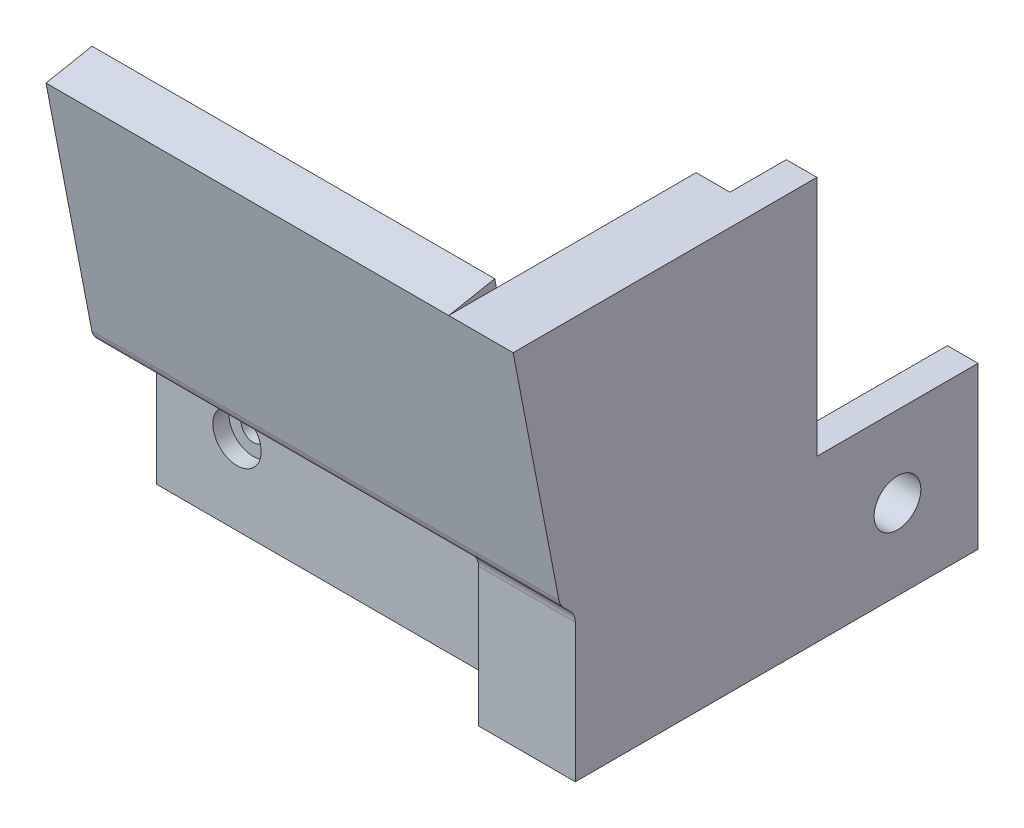
SolidWorks part; units mm, degrees
ref_plane "前视基准面" through (0, 0, 0) normal (0, 0, 1) x (1, 0, 0)
ref_plane "上视基准面" through (0, 0, 0) normal (0, 1, 0) x (1, 0, 0)
ref_plane "右视基准面" through (0, 0, 0) normal (1, 0, 0) x (0, 0, -1)
other "Configuration Table"
sketch "草图1" plane through (0, 0, 0) normal (1, 0, 0) x (0, 0, -1)
  line L0 (0, 0) -> (-10, 0)
  line L1 (-10, 0) -> (-17.7164, 40)
  line L2 (-17.7164, 40) -> (-12, 41.1027)
  line L3 (-12, 41.1027) -> (-6, 10)
  line L4 (-6, 10) -> (0, 10)
  line L5 (0, 10) -> (0, 0)
  dimension "D1" = 10
  dimension "D2" = 6
  dimension "D3" = 10
  dimension "D4" = 6
  dimension "D5" = 40
extrude "凸台-拉伸1" add sketch "草图1" along normal blind 50
sketch "草图2" plane through (0, 0, 0) normal (0, -1, 0) x (1, 0, 0)
  line L4 (0, 10) -> (0, 0)
  line L5 (0, 0) -> (50, 0)
  line L6 (50, 0) -> (50, 10)
  line L7 (50, 10) -> (0, 10)
  line L8 (0, 10) -> (0, 0)
  line L9 (0, 0) -> (50, 0)
  line L10 (50, 0) -> (50, 10)
  line L11 (50, 10) -> (0, 10)
  dimension "D1" = 0
extrude "凸台-拉伸2" add sketch "草图2" along normal blind 10
sketch "草图3" plane through (0, 0, 0) normal (-1, 0, 0) x (0, 0, 1)
  line L1 (0, 10) -> (10, 10)
  line L2 (0, 10) -> (0, -10)
  line L3 (0, -10) -> (10, -10)
  line L4 (10, 10) -> (10, -10)
extrude "凸台-拉伸3" add sketch "草图3" along normal blind 20
sketch "草图4" plane through (0, 10, 0) normal (0, 1, 0) x (1, 0, 0)
  line L1 (-20, 0) -> (0, 0)
  line L2 (-20, 0) -> (-20, -10)
  line L3 (-20, -10) -> (0, -10)
  line L4 (0, 0) -> (0, -10)
extrude "凸台-拉伸4" add sketch "草图4" along normal blind 30
sketch "草图5" plane through (50, 0, 0) normal (1, 0, 0) x (0, 0, -1)
  line L0 (-10, 10) -> (-11.9291, 10)
  line L1 (-17.7164, 40) -> (-10, 0) construction
  line L2 (-11.9291, 10) -> (-10, 0)
  line L3 (-10, 0) -> (-10, 10)
extrude "切除-拉伸1" cut sketch "草图5" against normal up to surface (50 mm away) up to face at (0, 27.9595, 12.4291)
chamfer "倒角1" distance 2 angle 45 1 edges at (25, 10, 10)
sketch "草图9" plane through (0, 0, 10) normal (0, 0, 1) x (1, 0, 0)
  line L0 (-20, 40) -> (-10, 40) construction
  line L1 (-20, 40) -> (0, 40) construction
  line L2 (-10, 40) -> (-10, 20) construction
  line L3 (50, -10) -> (50, 0) construction
  line L4 (50, -10) -> (50, 8) construction
  line L5 (50, 0) -> (10, 0) construction
  line L6 (-20, -10) -> (-20, 40) construction
  circle A0 centre (-10, 20) radius 1.5
  circle A1 centre (10, 0) radius 1.5
  dimension "D3" = 3
  dimension "D5" = 3
  dimension "D4" = 30
  dimension "D1" = 10
  dimension "D2" = 20
extrude "切除-拉伸2" cut sketch "草图9" against normal through all
sketch "草图12" plane through (0, 0, 10) normal (0, 0, 1) x (1, 0, 0)
  line L6 (0, 30.7352) -> (0, 40)
  line L7 (0, 30.7352) -> (0, 40)
  line L8 (0, 40) -> (-20, 40)
  line L9 (50, -10) -> (50, 8)
  line L10 (50, 8) -> (0, 8)
  line L11 (0, 8) -> (0, 30.7352)
  line L15 (50, -10) -> (50, 8)
  line L16 (50, 8) -> (0, 8)
  line L17 (0, 8) -> (0, 30.7352)
  line L19 (0, 40) -> (-20, 40)
  line L20 (-20, 40) -> (-20, -10)
  line L21 (-20, 40) -> (-20, -10)
  line L22 (-20, -10) -> (50, -10)
  line L23 (-20, -10) -> (50, -10)
  dimension "D1" = 0
extrude "切除-拉伸4" cut sketch "草图12" against normal blind 6
sketch "草图13" plane through (0, 8, 0) normal (0, -1, 0) x (1, 0, 0)
  line L0 (50, 4) -> (0, 4) construction
  line L1 (0, 10) -> (4, 10)
  line L2 (0, 10) -> (0, 4)
  line L3 (0, 4) -> (4, 4)
  line L4 (4, 10) -> (4, 4)
  line L6 (50, 10) -> (46, 10)
  line L7 (50, 10) -> (50, 4)
  line L8 (50, 4) -> (46, 4)
  line L9 (46, 10) -> (46, 4)
  dimension "D1" = 4
  dimension "D2" = 4
extrude "凸台-拉伸12" add sketch "草图13" along normal up to surface (18 mm away) up to face at (15, -10, 2)
fillet "圆角2" radius 2 3 edges at (25, 9.9121, 11.9121) (48, 8, 10) (2, 8, 10)
sketch "草图15" plane through (0, 0, 0) normal (0, 0, -1) x (-1, 0, 0)
  line L0 (-25, 10) -> (-25, 20.01) construction
  line L1 (0, 40) -> (20, 40) construction
  line L2 (0, 40) -> (0, -10) construction
  line L3 (0, -10) -> (20, -10) construction
  line L4 (20, 40) -> (20, -10) construction
  line L5 (-50, 10) -> (0, 10) construction
  line L6 (-50, -10) -> (-70, -10)
  line L7 (-70, 40) -> (-70, -10)
  line L8 (-50, 40) -> (-70, 40)
  line L9 (-50, 40) -> (-50, -10)
  circle A0 centre (10, 20) radius 1.5 construction
  circle A1 centre (-60, 20) radius 1.5
extrude "凸台-拉伸14" add sketch "草图15" against normal up to surface (4 mm away) up to face at (-8.5, 20, 4)
sketch "草图16" plane through (0, 0, 4) normal (0, 0, 1) x (1, 0, 0)
  line L5 (-20, -10) -> (0, -10)
  line L6 (0, -10) -> (0, 10)
  line L7 (0, 10) -> (0, 40)
  line L8 (0, 40) -> (-20, 40)
  line L9 (-20, 40) -> (-20, -10)
  line L10 (-20, -10) -> (0, -10)
  line L11 (0, -10) -> (0, 10)
  line L12 (0, 10) -> (0, 40)
  line L13 (0, 40) -> (-20, 40)
  line L14 (-20, 40) -> (-20, -10)
  dimension "D1" = 0
extrude "切除-拉伸5" cut sketch "草图16" against normal up to surface (4 mm away) up to face at (-8.5, 20, 0)
sketch "草图17" plane through (0, 0, 4) normal (0, 0, 1) x (1, 0, 0)
  line L0 (70, -10) -> (50, -10) construction
  line L1 (70, 40) -> (54, 40)
  line L2 (70, 40) -> (70, -10)
  line L3 (70, -10) -> (54, -10)
  line L4 (54, 40) -> (54, -10)
  dimension "D1" = 16
extrude "切除-拉伸6" cut sketch "草图17" against normal up to surface (4 mm away) up to face at (11.5, 0, 0)
sketch "草图18" plane through (50, 0, 0) normal (-1, 0, 0) x (0, 0, 1)
  line L0 (0, 10) -> (6, 10)
  line L1 (6, 10) -> (7.9291, 20)
  line L2 (6, 10) -> (12, 41.1027) construction
  line L3 (7.9291, 20) -> (0, 20)
  line L4 (0, 10) -> (0, 40) construction
  line L5 (0, 20) -> (0, 10)
  dimension "D1" = 10
extrude "凸台-拉伸15" add sketch "草图18" along normal blind 10
sketch "草图20" plane through (0, 0, 0) normal (0, 0, -1) x (-1, 0, 0)
  line L1 (-50, 40) -> (-54, 40)
  line L2 (-50, 40) -> (-50, -10)
  line L3 (-50, -10) -> (-54, -10)
  line L4 (-54, 40) -> (-54, -10)
extrude "凸台-拉伸16" add sketch "草图20" along normal blind 20
sketch "草图23" plane through (54, 0, 0) normal (1, 0, 0) x (0, 0, -1)
  line L0 (-4, -10) -> (-4, 20) construction
  line L1 (-4, 12) -> (20, 12)
  line L2 (-4, 12) -> (-4, -10)
  line L3 (-4, -10) -> (20, -10)
  line L4 (20, 12) -> (20, -10)
  line L5 (-7.9291, 20) -> (-4, 20) construction
  dimension "D1" = 8
extrude "切除-拉伸9" cut sketch "草图23" against normal up to surface (4 mm away) up to face at (50, 13.687, 9.9675)
sketch "草图24" plane through (0, 0, 4) normal (0, 0, 1) x (1, 0, 0)
  line L5 (50, 12) -> (54, 12)
  line L6 (54, 12) -> (54, 40)
  line L7 (54, 40) -> (50, 40)
  line L8 (50, 40) -> (50, 20)
  line L9 (50, 20) -> (50, 12)
  line L10 (50, 12) -> (54, 12)
  line L11 (54, 12) -> (54, 40)
  line L12 (54, 40) -> (50, 40)
  line L13 (50, 40) -> (50, 20)
  line L14 (50, 20) -> (50, 12)
  dimension "D1" = 0
extrude "凸台-拉伸17" add sketch "草图24" along normal up to surface (13.7164 mm away) up to face at (25, 25.257, 14.8723)
sketch "草图25" plane through (0, 12, 0) normal (0, -1, 0) x (1, 0, 0)
  line L1 (50, 0) -> (54, 0)
  line L2 (50, 0) -> (50, 12.3149)
  line L3 (50, 12.3149) -> (54, 12.3149)
  line L4 (54, 0) -> (54, 12.3149)
extrude "凸台-拉伸18" add sketch "草图25" along normal up to surface (22 mm away) up to face at (25, -10, 6)
sketch "草图26" plane through (50, 0, 0) normal (-1, 0, 0) x (0, 0, 1)
  line L5 (12.3149, -10) -> (12.3149, 12)
  line L6 (12.3149, 12) -> (12.0283, 10.5141)
  line L7 (11.4787, 9.4787) -> (10.5858, 8.5858)
  line L8 (10, 7.1716) -> (10, -10)
  line L9 (10, -10) -> (12.3149, -10)
  line L10 (12.3149, -10) -> (12.3149, 12)
  line L11 (12.3149, 12) -> (12.0283, 10.5141)
  line L12 (11.4787, 9.4787) -> (10.5858, 8.5858)
  line L13 (10, 7.1716) -> (10, -10)
  line L14 (10, -10) -> (12.3149, -10)
  arc A2 (11.4787, 9.4787) -> (12.0283, 10.5141) centre (10.0645, 10.8929) ccw
  arc A3 (10.5858, 8.5858) -> (10, 7.1716) centre (12, 7.1716) ccw
  arc A4 (11.4787, 9.4787) -> (12.0283, 10.5141) centre (10.0645, 10.8929) ccw
  arc A5 (10.5858, 8.5858) -> (10, 7.1716) centre (12, 7.1716) ccw
  dimension "D1" = 0
extrude "切除-拉伸10" cut sketch "草图26" against normal up to surface (4 mm away) up to face at (54, 13.7143, 0.3352)
sketch "草图27" plane through (4, 0, 0) normal (1, 0, 0) x (0, 0, -1)
  line L5 (-10, -10) -> (-4, -10)
  line L6 (-4, -10) -> (-4, 8)
  line L7 (-4, 8) -> (-10, 8)
  line L8 (-10, 8) -> (-10.5858, 8.5858)
  line L9 (-10, 7.1716) -> (-10, -10)
  line L10 (-10, -10) -> (-4, -10)
  line L11 (-4, -10) -> (-4, 8)
  line L12 (-4, 8) -> (-10, 8)
  line L13 (-10, 8) -> (-10.5858, 8.5858)
  line L14 (-10, 7.1716) -> (-10, -10)
  arc A1 (-10, 7.1716) -> (-10.5858, 8.5858) centre (-12, 7.1716) ccw
  arc A2 (-10, 7.1716) -> (-10.5858, 8.5858) centre (-12, 7.1716) ccw
  dimension "D1" = 0
extrude "切除-拉伸11" cut sketch "草图27" against normal up to surface (4 mm away) up to face at (0, 11.687, 8.9746)
sketch "草图31" plane through (40, 0, 0) normal (-1, 0, 0) x (0, 0, 1)
  line L4 (0, 20) -> (0, 10)
  line L5 (0, 10) -> (6, 10)
  line L6 (6, 10) -> (7.9291, 20)
  line L7 (7.9291, 20) -> (0, 20)
  line L8 (0, 20) -> (0, 10)
  line L9 (0, 10) -> (6, 10)
  line L10 (6, 10) -> (7.9291, 20)
  line L11 (7.9291, 20) -> (0, 20)
  dimension "D1" = 0
extrude "切除-拉伸14" cut sketch "草图31" against normal blind 10
sketch "草图32" plane through (54, 0, 0) normal (1, 0, 0) x (0, 0, -1)
  line L8 (-10, 7.1716) -> (-10, -10)
  line L9 (-10, -10) -> (0, -10)
  line L10 (0, -10) -> (0, 12)
  line L11 (0, 12) -> (20, 12)
  line L12 (20, 12) -> (20, 40)
  line L13 (20, 40) -> (-17.7164, 40)
  line L14 (-17.7164, 40) -> (-12.0283, 10.5141)
  line L15 (-11.4787, 9.4787) -> (-10.5858, 8.5858)
  line L16 (-10, 7.1716) -> (-10, -10)
  line L17 (-10, -10) -> (0, -10)
  line L18 (0, -10) -> (0, 12)
  line L19 (0, 12) -> (20, 12)
  line L20 (20, 12) -> (20, 40)
  line L21 (20, 40) -> (-17.7164, 40)
  line L22 (-17.7164, 40) -> (-12.0283, 10.5141)
  line L23 (-11.4787, 9.4787) -> (-10.5858, 8.5858)
  arc A2 (-10, 7.1716) -> (-10.5858, 8.5858) centre (-12, 7.1716) ccw
  arc A3 (-12.0283, 10.5141) -> (-11.4787, 9.4787) centre (-10.0645, 10.8929) ccw
  arc A4 (-10, 7.1716) -> (-10.5858, 8.5858) centre (-12, 7.1716) ccw
  arc A5 (-12.0283, 10.5141) -> (-11.4787, 9.4787) centre (-10.0645, 10.8929) ccw
  dimension "D1" = 0
extrude "凸台-拉伸19" add sketch "草图32" along normal blind 4
sketch "草图35" plane through (0, 12, 0) normal (0, -1, 0) x (1, 0, 0)
  line L4 (58, 0) -> (50, 0)
  line L5 (50, 0) -> (50, -20)
  line L6 (50, -20) -> (58, -20)
  line L7 (58, -20) -> (58, 0)
  line L8 (58, 0) -> (50, 0)
  line L9 (50, 0) -> (50, -20)
  line L10 (50, -20) -> (58, -20)
  line L11 (58, -20) -> (58, 0)
  dimension "D1" = 0
extrude "凸台-拉伸20" add sketch "草图35" along normal up to surface (22 mm away) up to face at (34.6667, -10, 4.6667)
sketch "草图36" plane through (0, 0, -20) normal (0, 0, -1) x (-1, 0, 0)
  line L0 (-58, -10) -> (-58, 40) construction
  line L1 (-50, -10) -> (-58, -10)
  line L2 (-50, -10) -> (-50, 10)
  line L3 (-50, 10) -> (-58, 10)
  line L4 (-58, -10) -> (-58, 10)
  dimension "D1" = 20
extrude "凸台-拉伸21" add sketch "草图36" along normal blind 20
sketch "草图37" plane through (50, 0, 0) normal (-1, 0, 0) x (0, 0, 1)
  line L0 (-20, 40) -> (-13, 40)
  line L1 (11.7873, 40) -> (-20, 40) construction
  line L2 (-13, 40) -> (-13, 3)
  line L3 (-13, 3) -> (-40, 3)
  line L4 (-40, -10) -> (-40, 10) construction
  line L5 (-40, 3) -> (-40, 10)
  line L6 (-40, 10) -> (-20, 10)
  line L7 (-20, 10) -> (-20, 40)
  dimension "D1" = 7
  dimension "D2" = 7
extrude "切除-拉伸17" cut sketch "草图37" against normal blind 4.2
sketch "草图38" plane through (58, 0, 0) normal (1, 0, 0) x (0, 0, -1)
  line L0 (40, 0) -> (30, 0) construction
  line L1 (40, 10) -> (40, -10) construction
  circle A0 centre (30, 0) radius 1.5
  dimension "D2" = 3
  dimension "D1" = 10
extrude "切除-拉伸18" cut sketch "草图38" against normal blind 10
sketch "草图39" plane through (58, 0, 0) normal (1, 0, 0) x (0, 0, -1)
  circle A0 centre (30, 0) radius 2.9
  dimension "D1" = 5.8
extrude "切除-拉伸19" cut sketch "草图39" against normal offset from surface (6 mm away) 2 up to face at (50, 0, -28.5)
sketch "草图40" plane through (0, 0, 4) normal (0, 0, 1) x (1, 0, 0)
  circle A0 centre (10, 0) radius 3
  dimension "D1" = 6
extrude "切除-拉伸20" cut sketch "草图40" against normal offset from surface (2 mm away) 2 up to face at (11.5, 0, 0)
